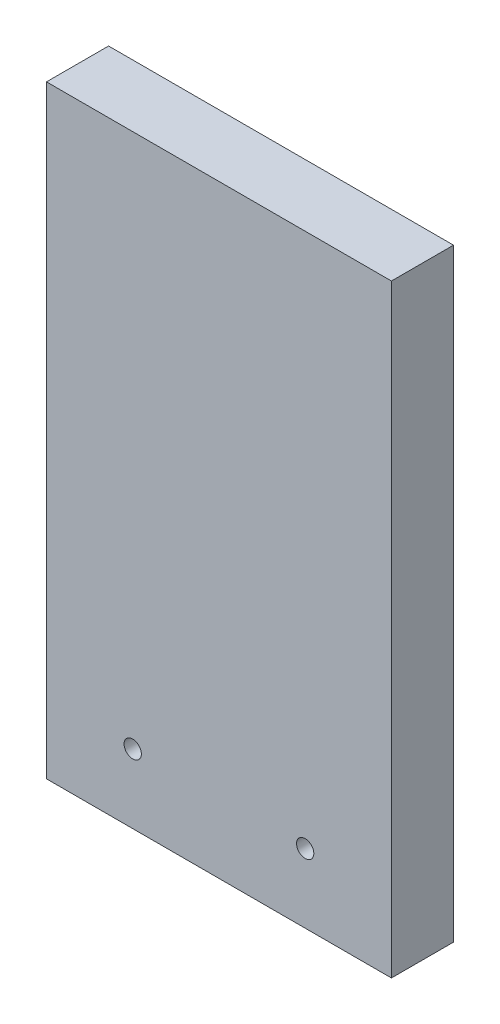
SolidWorks part; units mm, degrees
ref_plane "Plano frontal" through (0, 0, 0) normal (0, 0, 1) x (1, 0, 0)
ref_plane "Plano superior" through (0, 0, 0) normal (0, 1, 0) x (1, 0, 0)
ref_plane "Plano direito" through (0, 0, 0) normal (1, 0, 0) x (0, 0, -1)
sketch "Esboço1" plane through (0, 0, 0) normal (0, 0, 1) x (1, 0, 0)
  line L1 (95.8436, 73.8592) -> (85.8436, 73.8592)
  line L2 (95.8436, 73.8592) -> (95.8436, 56.3592)
  line L3 (95.8436, 56.3592) -> (85.8436, 56.3592)
  line L4 (85.8436, 73.8592) -> (85.8436, 56.3592)
  dimension "D1" = 10
  dimension "D2" = 17.5
extrude "Ressalto-extrusão1" add sketch "Esboço1" along normal blind 1.8
sketch "Esboço2" plane through (0, 0, 1.8) normal (0, 0, 1) x (1, 0, 0)
  line L0 (85.8436, 73.8592) -> (90.8436, 73.8592) construction
  line L1 (95.8436, 73.8592) -> (85.8436, 73.8592) construction
  line L2 (90.8436, 73.8592) -> (95.8436, 73.8592) construction
  line L3 (88.3436, 73.8592) -> (88.3436, 58.3592) construction
  line L4 (88.3436, 58.3592) -> (93.3436, 58.3592) construction
  line L5 (93.3436, 58.3592) -> (93.3436, 73.8592) construction
  circle A0 centre (88.3436, 58.3592) radius 0.25
  circle A1 centre (93.3436, 58.3592) radius 0.25
  point P12 (0, 0)
  point P14 (93.4504, 71.8592)
  dimension "D1" = 0.5
  dimension "D2" = 15.5
extrude "Corte-extrusão1" cut sketch "Esboço2" against normal through all contours A0 | A1
